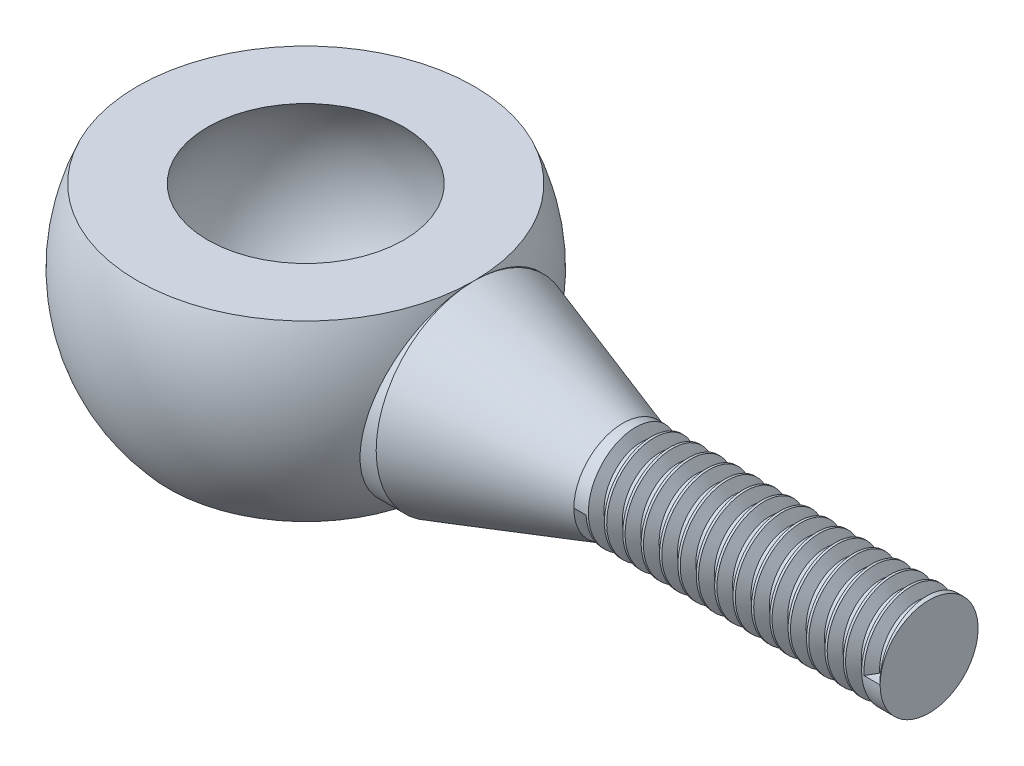
SolidWorks part; units mm, degrees
ref_plane "Front Plane" through (0, 0, 0) normal (0, 0, 1) x (1, 0, 0)
ref_plane "Top Plane" through (0, 0, 0) normal (0, 1, 0) x (1, 0, 0)
ref_plane "Right Plane" through (0, 0, 0) normal (1, 0, 0) x (0, 0, -1)
sketch "Sketch1" plane through (0, 0, 0) normal (0, 0, 1) x (1, 0, 0)
  line L0 (0, 6.906) -> (0, -5.2708) construction
  line L5 (4, -10) -> (11.1803, -10)
  line L6 (4, -9.1652) -> (4, -10)
  line L8 (8, 6) -> (13.7477, 6)
  arc A0 (11.1803, -10) -> (13.7477, 6) centre (0, 0) ccw
  arc A1 (4, -9.1652) -> (8, 6) centre (0, 0) ccw
  dimension "D1" = 30
  dimension "D4" = 20
revolve "Revolve1" add sketch "Sketch1" angle 360 about L0
sketch "Sketch2" plane through (0, 0, 0) normal (0, 0, 1) x (1, 0, 0)
  line L0 (13.7477, 6) -> (25.8846, 2)
  line L1 (25.8846, 2) -> (25.8846, -2)
  line L2 (25.8846, -2) -> (13.7477, -2)
  line L3 (13.7477, -2) -> (13.7477, 6)
  line L4 (6.5415, -2) -> (11.386, -2) construction
  line L5 (8, 6) -> (-8, 6) construction
  dimension "D1" = 8
  dimension "D2" = 4
revolve "Revolve2" add sketch "Sketch2" angle 360 about L4
sketch "Sketch4" plane through (13.7477, 0, 0) normal (-1, 0, 0) x (0, 0, 1)
  circle A0 centre (0, -2) radius 8
  circle A1 centre (0, -2) radius 8 construction
extrude "Boss-Extrude1" add sketch "Sketch4" along normal up to next
sketch "Sketch5" plane through (25.8846, 0, 0) normal (1, 0, 0) x (0, 0, -1)
  circle A0 centre (0, -2) radius 4
  circle A1 centre (0, -2) radius 4 construction
extrude "Boss-Extrude2" add sketch "Sketch5" along normal blind 25
thread "Thread1" pitch 1.5 method cut profile "Thread Profile1" start angle 0, offset 0, length 24, pitch 1.5, diameter 8
ref_plane "Plane1" through (50.8846, -2, 4) normal (0, -1, 0) x (0, 0, 1)
sketch "Thread Profile1" plane through (50.8846, -2, 4) normal (0, -1, 0) x (0, 0, 1)
  line L0 (0, 0) -> (0, 1.5) construction
  line L11 (0, 0) -> (0, 1.3125)
  line L12 (0, 1.3125) -> (-0.8119, 0.8437)
  line L13 (-0.8119, 0.8437) -> (-0.8119, 0.4687)
  line L15 (-0.8119, 0.4687) -> (0, 0)
  line L17 (-0.8119, 0.6562) -> (0, 0.6562) construction
  point P2 (0, 0)
  dimension "Pitch" = 1.5
  dimension "Profile_Angle" = 60
  dimension "Profile_Land" = 0.375
  dimension "Profile_Height" = 0.8119
sketch "Sketch6" plane through (0, 6, 0) normal (0, 1, 0) x (1, 0, 0)
  line L0 (0, 0) -> (25.8846, 0)
  dimension "D1" = 25.8846
